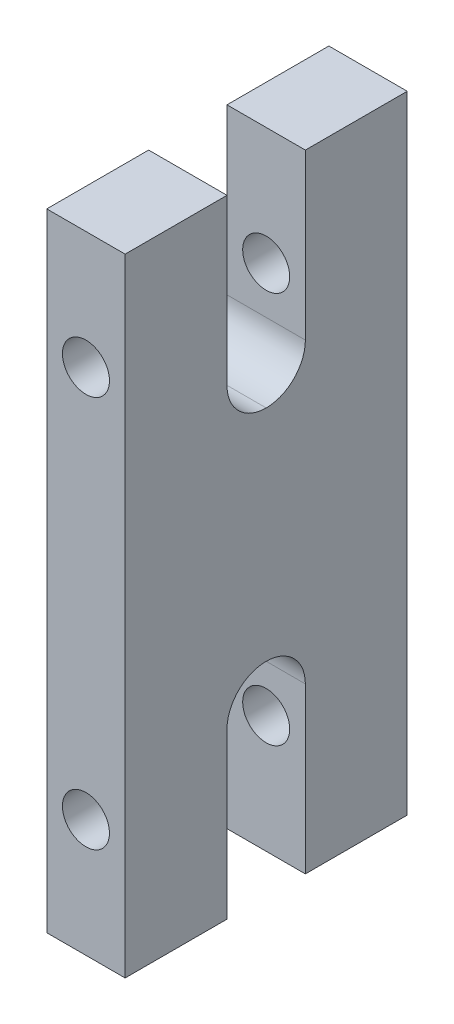
SolidWorks part; units mm, degrees
material "POM 乙缩醛共聚物"
ref_plane "前视基准面" through (0, 0, 0) normal (0, 0, 1) x (1, 0, 0)
ref_plane "上视基准面" through (0, 0, 0) normal (0, 1, 0) x (1, 0, 0)
ref_plane "右视基准面" through (0, 0, 0) normal (1, 0, 0) x (0, 0, -1)
sketch "草图1" plane through (0, 0, 0) normal (1, 0, 0) x (0, 0, -1)
  line L0 (-2.5, 20) -> (-2.5, 7)
  line L1 (-9, 20) -> (-2.5, 20)
  line L2 (-9, 20) -> (-9, -20)
  line L3 (-9, -20) -> (-2.5, -20)
  line L4 (9, 20) -> (9, -20)
  line L5 (-9, 20) -> (9, -20) construction
  line L6 (-9, -20) -> (9, 20) construction
  line L7 (-2.5, 7) -> (2.5, 7)
  line L8 (2.5, 7) -> (2.5, 20)
  line L9 (-9, 0) -> (9, 0) construction
  line L10 (2.5, -7) -> (2.5, -20)
  line L11 (-2.5, -7) -> (2.5, -7)
  line L12 (-2.5, -20) -> (-2.5, -7)
  line L13 (2.5, -20) -> (9, -20)
  line L14 (2.5, 20) -> (9, 20)
  point P0 (0, 0)
  dimension "D1" = 40
  dimension "D2" = 18
  dimension "D3" = 5
  dimension "D4" = 13
  dimension "D5" = 2.5
extrude "凸台-拉伸1" add sketch "草图1" along normal blind 5
sketch "草图2" plane through (0, 0, 9) normal (0, 0, 1) x (1, 0, 0)
  line L0 (5, 20) -> (0, 20) construction
  line L1 (0, 0) -> (5, 0) construction
  line L2 (5, 20) -> (5, -20) construction
  circle A0 centre (2.5, 12.5) radius 1.5
  circle A1 centre (2.5, -12.5) radius 1.5
  dimension "D1" = 3
  dimension "D2" = 7.5
  dimension "D3" = 2.5
extrude "切除-拉伸1" cut sketch "草图2" against normal blind 21
fillet "圆角1" radius 2.5 4 edges at (2.5, 7, -2.5) (2.5, 7, 2.5) (2.5, -7, -2.5) (2.5, -7, 2.5)
